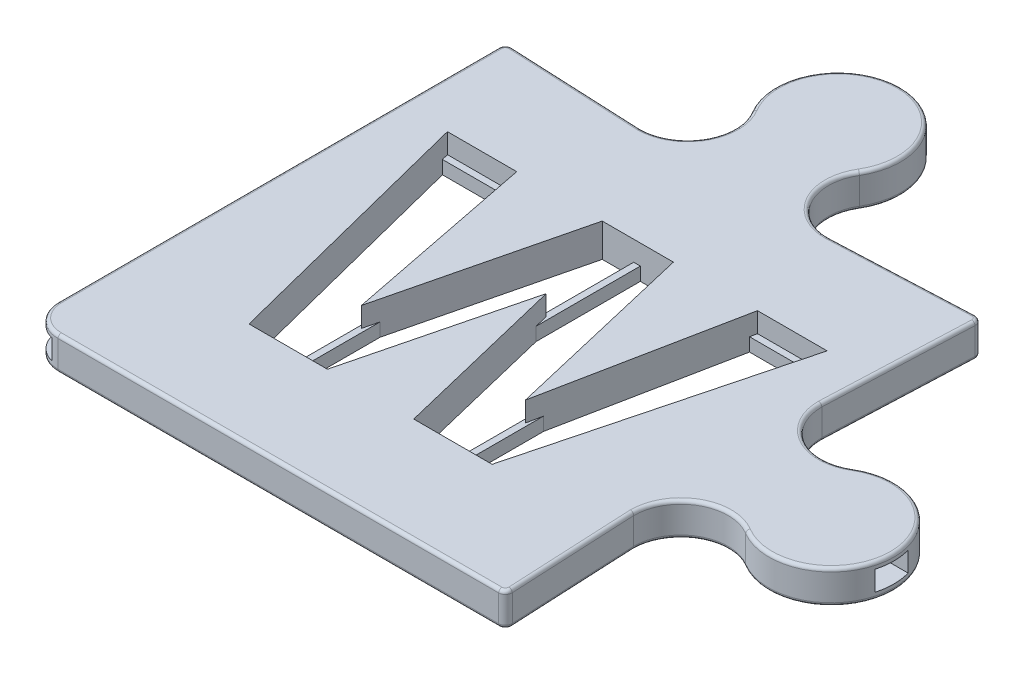
SolidWorks part; units mm, degrees
ref_plane "Front Plane" through (0, 0, 0) normal (0, 0, 1) x (1, 0, 0)
ref_plane "Top Plane" through (0, 0, 0) normal (0, 1, 0) x (1, 0, 0)
ref_plane "Right Plane" through (0, 0, 0) normal (1, 0, 0) x (0, 0, -1)
sketch "Sketch1" plane through (0, 0, 0) normal (0, 1, 0) x (1, 0, 0)
  line L0 (-31, -36) -> (37, -36) construction
  line L1 (-36, 37) -> (-36, -31) construction
  line L2 (-14.1421, 36) -> (-36, 37) construction
  line L3 (37, 37) -> (14.1421, 36) construction
  line L4 (36, 13.1421) -> (37, 37) construction
  line L5 (37, -36) -> (36, -15.1421) construction
  line L6 (-35.4, 36.3719) -> (-35.4, -31)
  line L7 (-36, 36) -> (36, 36) construction
  line L8 (-36, 36) -> (-36, -36) construction
  line L9 (-36, -36) -> (36, -36) construction
  line L10 (36, 36) -> (36, -36) construction
  line L11 (-31, -35.4) -> (36.3705, -35.4)
  line L12 (36.3705, -35.4) -> (35.4, -15.1568)
  line L13 (35.4, 13.155) -> (36.3732, 36.372)
  line L14 (36.3732, 36.372) -> (14.1555, 35.4)
  line L15 (-14.1562, 35.4) -> (-35.4, 36.3719)
  line L16 (-30, -24) -> (30, -24) construction
  line L17 (-30, 29) -> (30, 29) construction
  line L18 (-30, 29) -> (-30, -31) construction
  line L19 (-30, -31) -> (30, -31) construction
  line L20 (30, 29) -> (30, -31) construction
  line L21 (-30, 24) -> (30, 24) construction
  line L22 (-30, 24) -> (-30, -26) construction
  line L23 (-30, -26) -> (30, -26) construction
  line L24 (30, 24) -> (30, -26) construction
  arc A0 (-36, -31) -> (-31, -36) centre (-31, -31) ccw construction
  arc A1 (-14.1421, 36) -> (-8.571, 45.8485) centre (-14.1421, 42.5) ccw construction
  arc A2 (8.571, 45.8485) -> (-8.571, 45.8485) centre (0, 51) ccw construction
  arc A3 (8.571, 45.8485) -> (14.1421, 36) centre (14.1421, 42.5) ccw construction
  arc A4 (36, 13.1421) -> (45.8485, 7.571) centre (42.5, 13.1421) ccw construction
  arc A5 (45.8485, -9.571) -> (45.8485, 7.571) centre (51, -1) ccw construction
  arc A6 (45.8485, -9.571) -> (36, -15.1421) centre (42.5, -15.1421) ccw construction
  arc A7 (-35.4, -31) -> (-31, -35.4) centre (-31, -31) ccw
  arc A8 (46.1576, -9.0567) -> (35.4, -15.1568) centre (42.5, -15.1421) ccw
  arc A9 (46.1576, -9.0567) -> (46.1576, 7.0567) centre (51, -1) ccw
  arc A10 (35.4, 13.155) -> (46.1576, 7.0567) centre (42.5, 13.1421) ccw
  arc A11 (8.0567, 46.1576) -> (14.1555, 35.4) centre (14.1421, 42.5) ccw
  arc A12 (8.0567, 46.1576) -> (-8.0567, 46.1576) centre (0, 51) ccw
  arc A13 (-14.1562, 35.4) -> (-8.0567, 46.1576) centre (-14.1421, 42.5) ccw
  point P32 (36, 0)
  point P34 (0, 36)
  dimension "D5" = 6.5
  dimension "D6" = 10
  dimension "D7" = 6.5
  dimension "D13" = 5
  dimension "D9" = 10
  dimension "D11" = 6.5
  dimension "D12" = 6.5
  dimension "D1" = 72
  dimension "D2" = 1
  dimension "D3" = 1
  dimension "D4" = 15
  dimension "D8" = 1
  dimension "D10" = 35
  dimension "D14" = 15
  dimension "D15" = 36
  dimension "D16" = 1
  dimension "D18" = 60
  dimension "D19" = 60
  dimension "D20" = 5
  dimension "D21" = 6
  dimension "D22" = 5
  dimension "D23" = 50
  dimension "D24" = 2
  dimension "D17" = 0.6
extrude "Boss-Extrude1" add sketch "Sketch1" along normal blind 5
sketch "Sketch6" plane through (0, 0, 0) normal (0, -1, 0) x (1, 0, 0)
  line L0 (-35.4, -36.3719) -> (-35.4, 31) construction
  line L1 (-35.4, 17.9) -> (-27.4, 17.9)
  line L2 (-35.4, 17.9) -> (-35.4, -16.1)
  line L3 (-35.4, -16.1) -> (-27.4, -16.1)
  line L4 (-27.4, 17.9) -> (-27.4, -16.1)
  line L5 (-31, 35.4) -> (36.3705, 35.4) construction
  line L6 (-35.4, 14.65) -> (-30.4, 14.65)
  line L7 (-35.4, 14.65) -> (-35.4, -12.85)
  line L8 (-35.4, -12.85) -> (-30.4, -12.85)
  line L9 (-30.4, 14.65) -> (-30.4, -12.85)
  point P15 (-27.4, 0.9)
  point P16 (-30.4, 0.9)
  line M28 (-35.4, 31) -> (-35.4, -36.3719)
  dimension "D1" = 8
  dimension "D2" = 20.75
  dimension "D3" = 27.5
  dimension "D4" = 5
  dimension "D5" = 34
extrude "Cut-Extrude3" cut sketch "Sketch6" against normal blind 3 from offset 1 contours L6 L9 L8 L3 L4 L1 M28 | L9 L6 L2 L8 region at (-29.8665, 0, 0.9) region at (-32.9, 0, 0.9) offset against normal yes
extrude "Cut-Extrude4" cut sketch "Sketch6<3>" against normal up to next contours L9 L6 L2 L8 region at (-32.9, 0, 0.9)
sketch "Sketch6<3>" plane through (0, 0, 0) normal (0, -1, 0) x (1, 0, 0) same geometry as "Sketch6"
sketch "Sketch8" plane through (0, 0, 0) normal (0, -1, 0) x (1, 0, 0)
  line L1 (-2.5, -51.4) -> (2.5, -51.4)
  line L2 (-2.5, -51.4) -> (-2.5, -60.4)
  line L3 (-2.5, -60.4) -> (2.5, -60.4)
  line L4 (2.5, -51.4) -> (2.5, -60.4)
  line L5 (51.4, 3.5) -> (60.4, 3.5)
  line L6 (51.4, 3.5) -> (51.4, -1.5)
  line L7 (51.4, -1.5) -> (60.4, -1.5)
  line L8 (60.4, 3.5) -> (60.4, -1.5)
  arc A0 (-8.0567, -46.1576) -> (8.0567, -46.1576) centre (0, -51) ccw construction
  arc A1 (46.1576, -7.0567) -> (46.1576, 9.0567) centre (51, 1) ccw construction
  point P4 (0, -60.4)
  point P13 (60.4, 1)
  dimension "D1" = 5
  dimension "D2" = 9
  dimension "D3" = 5
  dimension "D4" = 9
extrude "Cut-Extrude5" cut sketch "Sketch8" against normal blind 3 from offset 1 offset against normal yes
sketch "Sketch9" plane through (0, 0, 0) normal (0, -1, 0) x (1, 0, 0)
  line L0 (-31, 35.4) -> (36.3705, 35.4) construction
  line L1 (-35.4, 14.65) -> (-35.4, 31) construction
  line L2 (-31.7636, 35.3332) -> (-35.4, 31) construction
  line L3 (-33.2571, 29.735) -> (-30.0429, 33.565) construction
  line L4 (-30.0429, 33.565) -> (-33.2571, 29.735) construction
  line L5 (-30.0429, 33.565) -> (-32.7119, 35.8048)
  line L6 (-33.2571, 29.735) -> (-35.926, 31.9747)
  line L7 (-32.7119, 35.8048) -> (-35.926, 31.9747)
  circle A0 centre (-31.65, 31.65) radius 2.5
  arc A1 (-31, 35.4) -> (-35.4, 31) centre (-31, 31) ccw construction
  arc M41 (-31, 35.4) -> (-35.4, 31) centre (-31, 31) ccw
  dimension "D1" = 5
  dimension "D3" = 3.75
  dimension "D4" = 5.6569
  dimension "D2" = 3.75
extrude "Cut-Extrude6" cut sketch "Sketch9" against normal blind 3 from offset 1 contours A0 L5 L6 M41 | A0 L5 region at (-33.6239, 0, 33.3064) region at (-31.65, 0, 31.65) offset against normal yes
sketch "Sketch11" plane through (-35.4, 0, 0) normal (-1, 0, 0) x (0, 0, 1)
  line L0 (-13.155, 0) -> (-36.372, 0) construction
  line L1 (-25.1, 3) -> (-19.1, 3)
  line L2 (-25.1, 3) -> (-25.1, 1.5)
  line L3 (-25.1, 1.5) -> (-19.1, 1.5)
  line L4 (-19.1, 3) -> (-19.1, 1.5)
  line L5 (-16.1, 4) -> (-16.1, 1) construction
  line L6 (35.4, 0) -> (15.1568, 0) construction
  line L7 (20.9, 3) -> (26.9, 3)
  line L8 (20.9, 3) -> (20.9, 1.5)
  line L9 (20.9, 1.5) -> (26.9, 1.5)
  line L10 (26.9, 3) -> (26.9, 1.5)
  line L12 (17.9, 4) -> (17.9, 1) construction
  dimension "D1" = 3
  dimension "D2" = 1.5
  dimension "D3" = 3
  dimension "D4" = 6
  dimension "D5" = 3
  dimension "D6" = 1.5
  dimension "D7" = 6
  dimension "D8" = 3
fillet "Fillet1" radius 0.5 17 edges at (-35.4, 0, 22.825) (-34.1113, 0, 34.1113) (2.6853, 0, 35.4) (35.8853, 0, 25.2784) (38.9978, 0, 8.966) (60.4, 0, 1) (38.9986, 0, -6.9655) (35.8866, 0, -24.7635) (25.2643, 0, -35.886) (7.9657, 0, -38.9984) (0, 0, -60.4) (-7.9658, 0, -38.9981) (-24.7781, 0, -35.886) (-35.4, 0, -24.611) (-32.9, 0, -12.85) (-30.4, 0, 0.9) (-32.9, 0, 14.65)
fillet "Fillet2" radius 0.5 13 edges at (-7.9658, 5, -38.9981) (0, 5, -60.4) (7.9657, 5, -38.9984) (25.2643, 5, -35.886) (35.8866, 5, -24.7635) (38.9986, 5, -6.9655) (60.4, 5, 1) (38.9978, 5, 8.966) (35.8853, 5, 25.2784) (2.6853, 5, 35.4) (-34.1113, 5, 34.1113) (-35.4, 5, -2.686) (-24.7781, 5, -35.886)
fillet "Fillet3" radius 1 9 edges at (36.2202, 0.1464, -36.2187) (36.2202, 4.8536, -36.2187) (36.3732, 2.5, -36.372) (-35.2536, 0.1464, -36.2186) (-35.2536, 4.8536, -36.2186) (36.2169, 0.1464, 35.2536) (36.2169, 4.8536, 35.2536) (36.3705, 2.5, 35.4) (-35.4, 2.5, -36.3719)
extrude "Cut-Extrude9" cut sketch "Sketch11" against normal blind 3
chamfer "Chamfer1" distance 1 angle 50 2 edges at (-35.4, 1.5, 23.9) (-35.4, 1.5, -22.1) first distance on face at (-35.4, 2.25, -22.1)
sketch "Sketch12" plane through (0, 5, 0) normal (0, 1, 0) x (1, 0, 0)
  text T0 "W" font "Poppins" height 40
  point P1 (-13.5058, -7.7493)
  point P2 (-24.0706, -10.3228)
  point P3 (-26.2378, -17.366)
  point P4 (-28.4049, -19.5331)
  point P5 (-29.0821, -19.6686)
  point P6 (-30.5994, -19.937)
  point P7 (-29.5926, -19.6272)
extrude "Cut-Extrude10" cut sketch "Sketch12" against normal through all
sketch "Sketch13" plane through (0, 0, 0) normal (0, -1, 0) x (1, 0, 0)
  line L0 (-18.0263, 19.6272) -> (-28.1664, -20.3728) construction
  line L1 (-18.2798, 18.6272) -> (-5.9779, 18.6272)
  line L2 (-18.2798, 18.6272) -> (-18.2798, 19.6272)
  line L3 (-18.2798, 19.6272) -> (-5.9779, 19.6272)
  line L4 (-5.9779, 18.6272) -> (-5.9779, 19.6272)
  line L5 (6.7635, 19.6272) -> (0.3827, -6.696) construction
  line L6 (6.5211, 18.6272) -> (18.8214, 18.6272)
  line L7 (6.5211, 18.6272) -> (6.5211, 19.6272)
  line L8 (6.5211, 19.6272) -> (18.8214, 19.6272)
  line L9 (18.8214, 18.6272) -> (18.8214, 19.6272)
  line L10 (0.3827, -6.696) -> (-6.2291, 19.6272) construction
  line L11 (-0.1262, -4.67) -> (0.8738, -4.67)
  line L12 (-0.1262, -4.67) -> (-0.1262, -20.3728)
  line L13 (-0.1262, -20.3728) -> (0.8738, -20.3728)
  line L14 (0.8738, -4.67) -> (0.8738, -20.3728)
  line L15 (-4.8605, -20.3728) -> (5.8484, -20.3728) construction
  line L16 (-17.7377, -20.3728) -> (-11.9834, 8.7451) construction
  line L17 (-28.1664, -20.3728) -> (-17.5401, -20.3728)
  line L18 (-28.1664, -20.3728) -> (-28.1664, -19.3728)
  line L19 (-28.1664, -19.3728) -> (-17.5401, -19.3728)
  line L20 (-17.5401, -20.3728) -> (-17.5401, -19.3728)
  line L21 (12.691, 8.7451) -> (18.503, -20.3728) construction
  line L22 (28.9894, -20.3728) -> (18.3034, -20.3728)
  line L23 (28.9894, -20.3728) -> (28.9894, -19.3728)
  line L24 (28.9894, -19.3728) -> (18.3034, -19.3728)
  line L25 (18.3034, -20.3728) -> (18.3034, -19.3728)
  line L26 (5.8484, -20.3728) -> (12.691, 8.7451) construction
  line L27 (-12.4302, 6.4838) -> (-11.4302, 6.4838)
  line L28 (-12.4302, 6.4838) -> (-12.4302, 19.6272)
  line L29 (-12.4302, 19.6272) -> (-11.4302, 19.6272)
  line L30 (-11.4302, 6.4838) -> (-11.4302, 19.6272)
  line L31 (12.1503, 6.4441) -> (13.1503, 6.4441)
  line L32 (12.1503, 6.4441) -> (12.1503, 19.6272)
  line L33 (12.1503, 19.6272) -> (13.1503, 19.6272)
  line L34 (13.1503, 6.4441) -> (13.1503, 19.6272)
  line L35 (-6.2291, 19.6272) -> (-18.0263, 19.6272) construction
  line L36 (-11.9834, 8.7451) -> (-4.8605, -20.3728) construction
  line L37 (28.9894, -20.3728) -> (18.5607, 19.6272) construction
  line L38 (18.5607, 19.6272) -> (6.7635, 19.6272) construction
  point P44 (-13.4289, 19.6272)
  point P47 (-10.4755, 2.5808)
  point P50 (-5.6469, 17.3095)
  point P51 (19.2477, 16.992)
  point P54 (13.744, 3.4696)
  point P55 (-18.4893, 18.8007)
  point P58 (1.5544, -1.8622)
  line M43 (28.9894, -20.3728) -> (18.503, -20.3728)
  line M44 (18.503, -20.3728) -> (12.691, 8.7451)
  line M45 (12.691, 8.7451) -> (5.8484, -20.3728)
  line M46 (5.8484, -20.3728) -> (-4.8605, -20.3728)
  line M48 (-11.9834, 8.7451) -> (-17.7377, -20.3728)
  line M49 (-17.7377, -20.3728) -> (-28.1664, -20.3728)
  line M50 (-28.1664, -20.3728) -> (-18.0263, 19.6272)
  line M51 (-18.0263, 19.6272) -> (-6.2291, 19.6272)
  line M52 (-6.2291, 19.6272) -> (0.3827, -6.696)
  line M53 (0.3827, -6.696) -> (6.7635, 19.6272)
  line M54 (6.7635, 19.6272) -> (18.5607, 19.6272)
  line M55 (18.5607, 19.6272) -> (28.9894, -20.3728)
  dimension "D1" = 1
  dimension "D2" = 1
  dimension "D3" = 1
  dimension "D4" = 1
  dimension "D5" = 1
  dimension "D6" = 1
  dimension "D7" = 1
extrude "Boss-Extrude2" add sketch "Sketch13" against normal blind 2 contours L19 M50 M49 M48 | L14 L12 M53 M52 M46 | L24 M55 M44 M43 | L34 L6 L32 M44 M45 | L6 L32 M54 M53 | L34 L6 M55 M54 | L30 L1 M52 M51 | L1 L28 M51 M50 | L34 L33 L32 L31 | L28 L29 L30 L27 region at (-15.2921, 0, 19.1235) region at (0.3736, 0, -13.0163) region at (-22.8394, 0, -19.8733) region at (-8.7664, 0, 19.1232) region at (9.3958, 0, 19.1235) region at (12.6488, 0, 13.0909) region at (15.9212, 0, 19.1232) region at (23.6312, 0, -19.8733)
